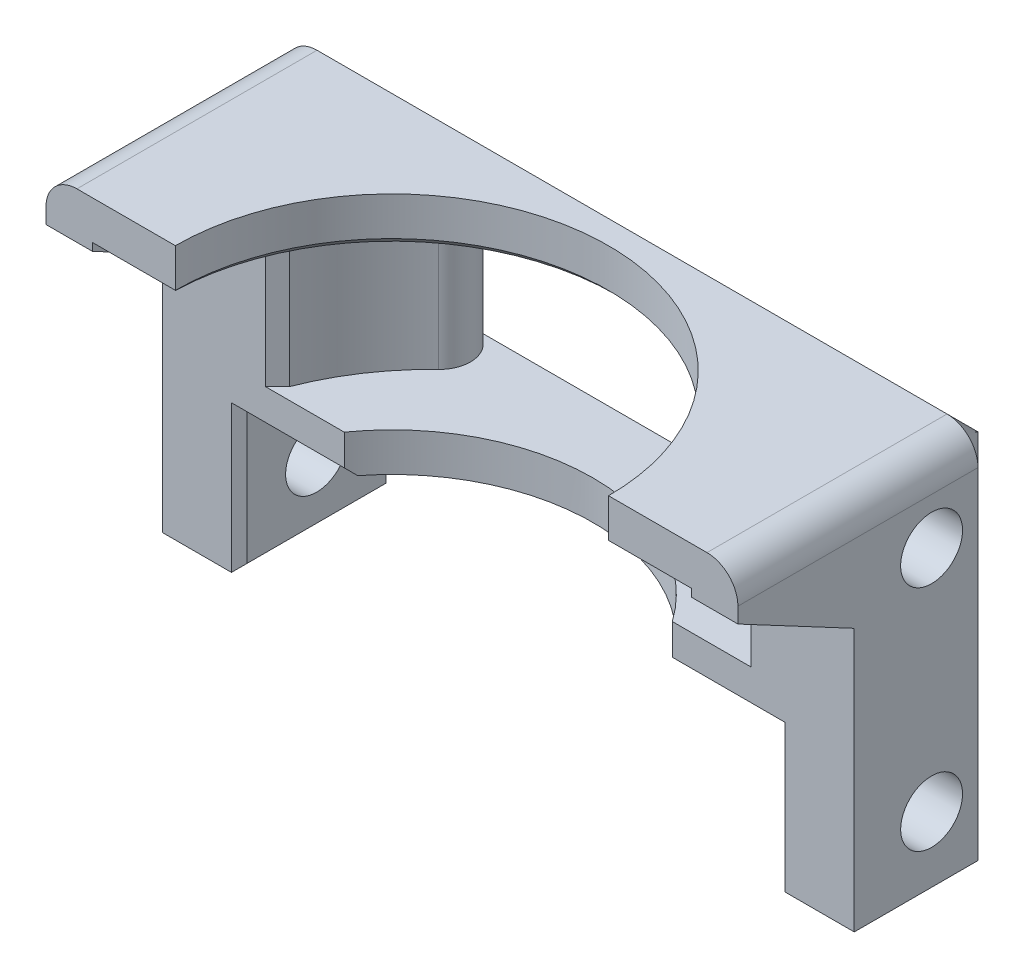
SolidWorks part; units mm, degrees
material "PEI"
ref_plane "前视基准面" through (0, 0, 0) normal (0, 0, 1) x (1, 0, 0)
ref_plane "上视基准面" through (0, 0, 0) normal (0, 1, 0) x (1, 0, 0)
ref_plane "右视基准面" through (0, 0, 0) normal (1, 0, 0) x (0, 0, -1)
other "Configuration Table"
sketch "草图1" plane through (0, 0, 0) normal (0, 0, 1) x (1, 0, 0)
  line L0 (-7.455, 0) -> (23.6667, 0) construction
  line L1 (0, 0) -> (4.97, 0)
  line L2 (4.97, 0) -> (4.97, 9)
  line L3 (4.97, 9) -> (39.75, 9)
  line L4 (39.75, 9) -> (39.75, 0)
  line L5 (39.75, 0) -> (44.73, 0)
  line L6 (44.73, 0) -> (44.73, 24)
  line L7 (44.73, 24) -> (0, 24)
  line L8 (0, 24) -> (0, 0)
  dimension "D1" = 4.97
  dimension "D2" = 34.78
  dimension "D3" = 44.73
  dimension "D4" = 9
  dimension "D5" = 24
extrude "凸台-拉伸1" add sketch "草图1" along normal blind 10
ref_plane "基准面1" through (0, 0, 15) normal (0, 0, -1) x (-1, 0, 0)
sketch "草图2" plane through (0, 0, 15) normal (0, 0, -1) x (-1, 0, 0)
  line L0 (-22.365, 28.1682) -> (-22.365, -7.2572) construction
  line L1 (-22.365, 21) -> (-6.365, 21)
  line L2 (-6.365, 21) -> (-6.365, 11.5)
  line L3 (-6.365, 11.5) -> (-22.365, 11.5)
  line L4 (-22.365, 11.5) -> (-22.365, 21)
  line L9 (0, 0) -> (0, 24)
  line L10 (0, 24) -> (-44.73, 24)
  line L11 (-44.73, 24) -> (-44.73, 0)
  line L12 (-44.73, 0) -> (-39.75, 0)
  line L13 (-39.75, 0) -> (-39.75, 9)
  line L14 (-39.75, 9) -> (-4.97, 9)
  line L15 (-4.97, 9) -> (-4.97, 0)
  line L16 (-4.97, 0) -> (0, 0)
  line L17 (0, 0) -> (0, 24)
  line L18 (0, 24) -> (-44.73, 24)
  line L19 (-44.73, 24) -> (-44.73, 0)
  line L20 (-44.73, 0) -> (-39.75, 0)
  line L21 (-39.75, 0) -> (-39.75, 9)
  line L22 (-39.75, 9) -> (-4.97, 9)
  line L23 (-4.97, 9) -> (-4.97, 0)
  line L24 (-4.97, 0) -> (0, 0)
  point P8 (-22.365, 24)
  dimension "D1" = 0
  dimension "D2" = 3
  dimension "D3" = 9.5
  dimension "D4" = 16
revolve "切除-旋转2" cut sketch "草图2" angle 360 about L0
sketch "草图4" plane through (0, 0, 0) normal (0, 0, -1) x (-1, 0, 0)
  line L0 (-44.73, 24) -> (0, 24) construction
  line L1 (-37.5637, 21) -> (-7.1663, 21) construction
  line L2 (-44.73, 24) -> (0, 24)
  line L3 (-37.5637, 21) -> (-7.1663, 21)
  line L4 (-44.73, 24) -> (-44.73, 21)
  line L5 (-44.73, 0) -> (-44.73, 24) construction
  line L6 (-44.73, 21) -> (-37.5637, 21)
  line L7 (0, 24) -> (0, 21)
  line L8 (0, 24) -> (0, 0) construction
  line L9 (0, 21) -> (-7.1663, 21)
extrude "凸台-拉伸2" add sketch "草图4" against normal blind 17.52
sketch "草图5" plane through (0, 24, 0) normal (0, 1, 0) x (1, 0, 0)
  line L4 (44.73, 0) -> (0, 0)
  line L5 (0, 0) -> (0, -17.52)
  line L6 (0, -17.52) -> (44.73, -17.52)
  line L7 (44.73, -17.52) -> (44.73, 0)
  line L10 (0, -17.52) -> (44.73, -17.52)
  arc A0 (36.365, -17.52) -> (8.365, -17.52) centre (22.365, -17.52) ccw
  arc A1 (38.365, -17.52) -> (6.365, -17.52) centre (22.365, -17.52) ccw
  dimension "D2" = 32
  dimension "D3" = 28
  dimension "D1" = 0
extrude "切除-拉伸1" cut sketch "草图5" against normal blind 3 contours L10 A0
sketch "草图6" plane through (0, 11.5, 0) normal (0, 1, 0) x (1, 0, 0)
  line L0 (7.1663, -10) -> (37.5637, -10) construction
  line L1 (11.7608, -10) -> (34.1739, -10)
  arc A0 (36.365, -17.52) -> (8.365, -17.52) centre (22.365, -17.52) ccw construction
  arc A1 (36.365, -17.52) -> (8.365, -17.52) centre (22.365, -17.52) ccw
  arc A2 (32.9692, -10) -> (11.7608, -10) centre (22.365, -17.52) ccw
  line M1 (7.1663, -10) -> (37.5637, -10)
  dimension "D1" = 13
extrude "切除-拉伸2" cut sketch "草图6" against normal up to surface (2.5 mm away) contours A2 M1 up to face at (22.36, 9, 5)
sketch "草图7" plane through (0, 0, 0) normal (-1, 0, 0) x (0, 0, 1)
  line L0 (10, 17) -> (10, 21)
  line L1 (10, 21) -> (10, 0) construction
  line L2 (10, 21) -> (17.52, 21)
  line L3 (17.52, 21) -> (10, 21) construction
  line L4 (17.52, 21) -> (10, 17)
  dimension "D1" = 4
extrude "凸台-拉伸3" add sketch "草图7" against normal blind 3
sketch "草图8" plane through (44.73, 0, 0) normal (1, 0, 0) x (0, 0, -1)
  line L3 (-17.52, 21) -> (-10, 17)
  line L4 (-10, 17) -> (-10, 21)
  line L5 (-10, 21) -> (-17.52, 21)
  line L6 (-17.52, 21) -> (-10, 17)
  line L7 (-10, 17) -> (-10, 21)
  line L8 (-10, 21) -> (-17.52, 21)
  dimension "D1" = 0
extrude "凸台-拉伸4" add sketch "草图8" against normal blind 3
fillet "圆角1" radius 2 2 edges at (44.73, 24, 8.76) (0, 24, 8.76)
chamfer "倒角1" distance 2 angle 45 5 edges at (44.73, 11, 0) (44.1442, 23.4142, 0) (22.365, 24, 0) (0.5858, 23.4142, 0) (0, 11, 0)
sketch "草图9" plane through (44.73, 0, 0) normal (1, 0, 0) x (0, 0, -1)
  line L0 (12.972, 24) -> (4.972, 24) construction
  line L1 (4.972, 14) -> (12.972, 14) construction
  line L2 (12.972, 24) -> (4.972, 24)
  line L3 (4.972, 14) -> (12.972, 14)
  line L4 (4.972, 14) -> (-10, 14)
  line L5 (-10, 0) -> (-10, 17) construction
  line L6 (4.972, 14) -> (-45.23, 14) construction
  line L7 (-10, 14) -> (-10, 24)
  line L8 (-45.23, 24) -> (4.972, 24) construction
  line L9 (0, 22) -> (0, 0) construction
  line L10 (0, 22) -> (0, 0)
  line L11 (0, 22) -> (0, 24)
  line L12 (0, 24) -> (-10, 24)
  line L13 (-10, 24) -> (0, 14)
  line L14 (0, 24) -> (-10, 14)
  circle A0 centre (-5, 19) radius 2
  dimension "D1" = 4
extrude "切除-拉伸3" cut sketch "草图9" against normal blind 6 contours L13 A0 L14 | L14 A0 L13 | L13 A0 L14 | L14 A0 L13
ref_plane "基准面2" through (22.365, 0, 0) normal (1, 0, 0) x (0, 0, -1)
mirror "镜向1" about plane through (22.365, 0, 0) normal (1, 0, 0) of "切除-拉伸3"
sketch "草图10" plane through (0, 0, 0) normal (-1, 0, 0) x (0, 0, 1)
  line L0 (0, 0) -> (0, 22) construction
  line L1 (10, 0) -> (0, 0)
  line L2 (10, 0) -> (10, 8.4755)
  line L3 (10, 8.4755) -> (0, 8.4755)
  line L4 (0, 0) -> (0, 8.4755)
  line L5 (10, 0) -> (0, 8.4755)
  line L6 (0, 0) -> (10, 8.4755)
  circle A0 centre (5, 4.2377) radius 2
  dimension "D1" = 4
extrude "切除-拉伸4" cut sketch "草图10" against normal up to surface (44.73 mm away) contours L6 A0 L5 | L5 A0 L6 | L6 A0 L5 | L5 A0 L6 up to face at (44.73, 19, 3)
chamfer "倒角2" distance 0.5 angle 45 13 edges at (4.97, 4.5, 0) (4.97, 0, 5) (4.97, 4.5, 10) (8.3654, 9, 10) (39.75, 4.5, 0) (39.75, 0, 5) (39.75, 4.5, 10) (36.3596, 9, 10) (37.5637, 16.25, 10) (7.1663, 16.25, 10) (22.365, 21, 3.52) (5.6825, 21, 17.52) (39.0475, 21, 17.52)
fillet "圆角2" radius 2 2 edges at (27.9328, 16.25, 0) (16.7972, 16.25, 0)
